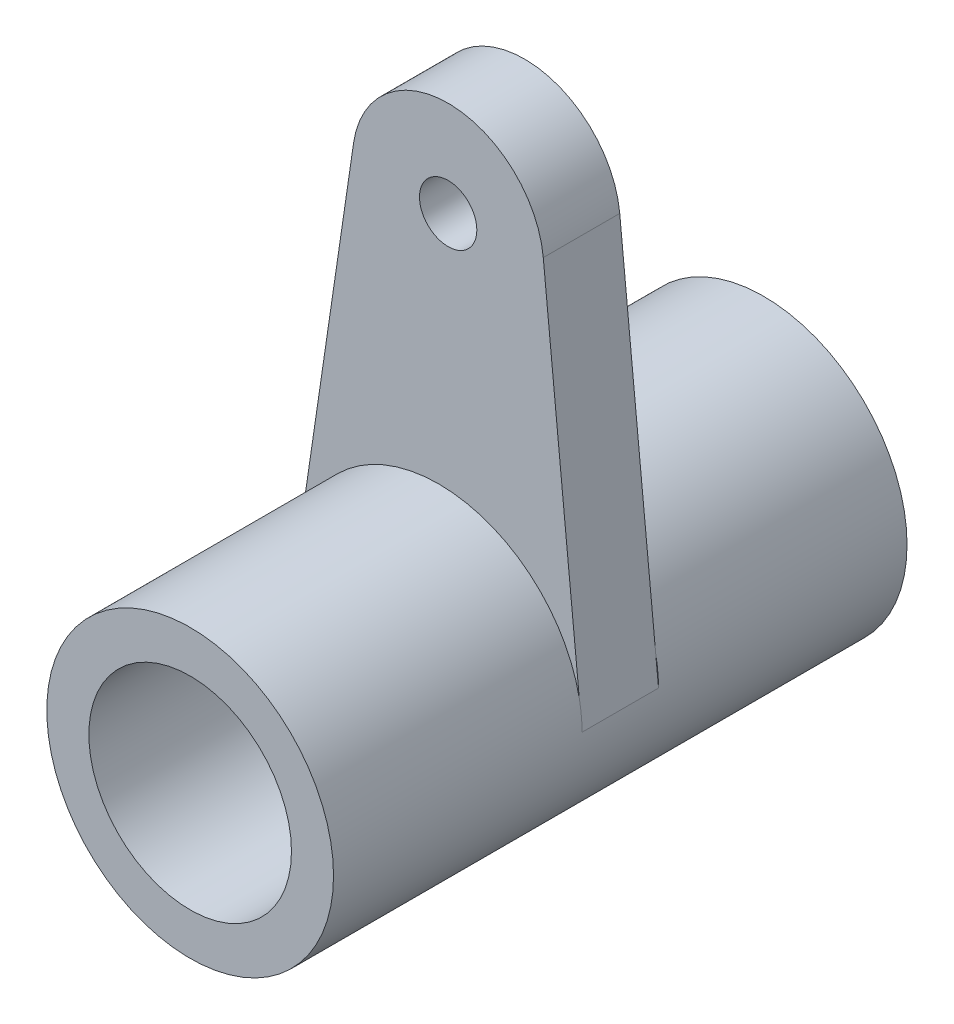
SolidWorks part; units mm, degrees
ref_plane "Plan de face" through (0, 0, 0) normal (0, 0, 1) x (1, 0, 0)
ref_plane "Plan de dessus" through (0, 0, 0) normal (0, 1, 0) x (1, 0, 0)
ref_plane "Plan de droite" through (0, 0, 0) normal (1, 0, 0) x (0, 0, -1)
sketch "Esquisse1" plane through (0, 0, 0) normal (0, 0, 1) x (1, 0, 0)
  line L0 (-7.5, 0) -> (-4.451, 20.7217)
  line L1 (5.4714, 20.4866) -> (7.5, 0)
  circle A2 centre (0, 0) radius 7.5
  circle A3 centre (0, 0) radius 5.3
  arc A4 (-4.451, 20.7217) -> (5.4714, 20.4866) centre (0.4957, 19.9939) cw
  circle A5 centre (0.4957, 19.9939) radius 1.5
  dimension "D1" = 5.3
  dimension "D2" = 7.5
  dimension "D4" = 5
  dimension "D5" = 3
  dimension "D3" = 20
extrude "Boss.-Extru.2" add sketch "Esquisse1" along normal blind 2 and the other way blind 2 contours A4 L0 A2 L1 | A2 L1 L0 A3 region at (-7.1312, 1.0493, 0) region at (0.3682, 14.3218, 0)
sketch "Esquisse2" plane through (0, 0, 2) normal (0, 0, 1) x (1, 0, 0)
  circle A0 centre (0, 0) radius 5.3
  circle A1 centre (0, 0) radius 7.5
  dimension "D1" = 10.6
  dimension "D2" = 15
extrude "Boss.-Extru.3" add sketch "Esquisse2" along normal blind 13
mirror "Symétrie1" about plane through (0, 0, 0) normal (0, 0, 1) of "Boss.-Extru.3"
